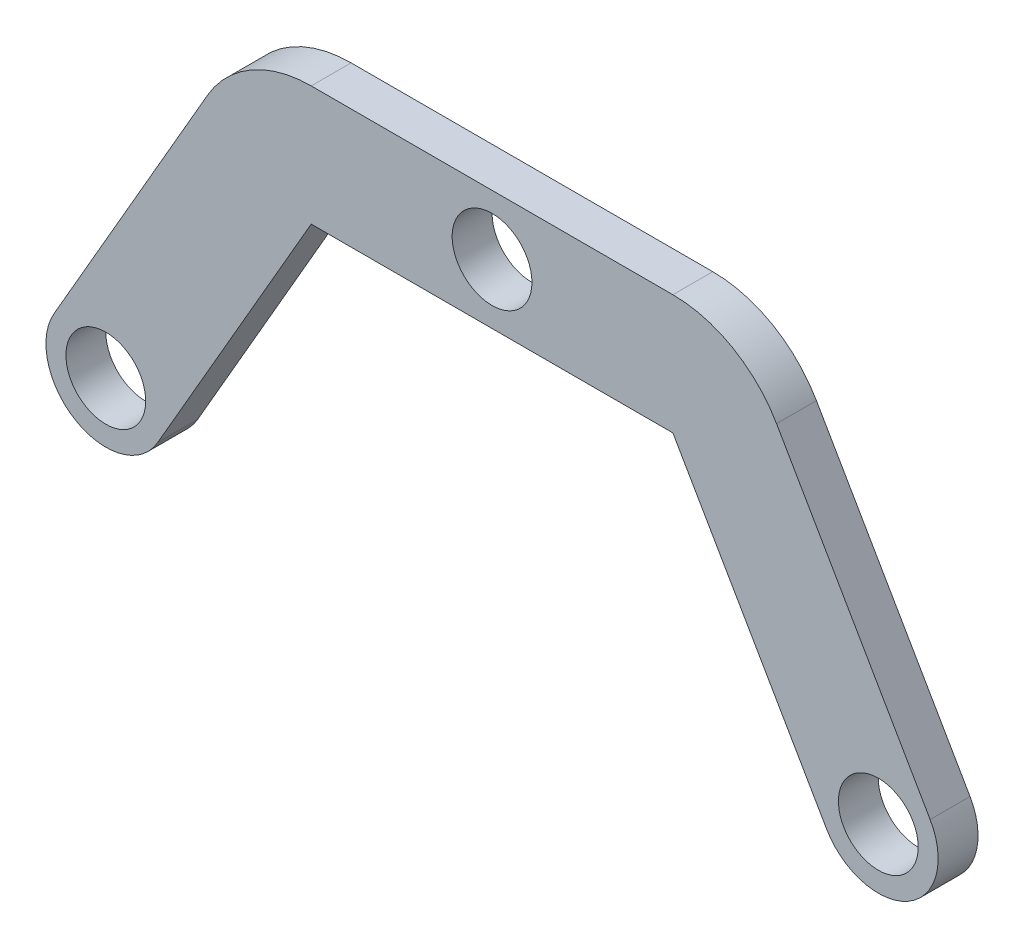
SolidWorks part; units mm, degrees
ref_plane "Front Plane" through (0, 0, 0) normal (0, 0, 1) x (1, 0, 0)
ref_plane "Top Plane" through (0, 0, 0) normal (0, 1, 0) x (1, 0, 0)
ref_plane "Right Plane" through (0, 0, 0) normal (1, 0, 0) x (0, 0, -1)
sketch "Sketch1" plane through (0, 0, 0) normal (0, 0, 1) x (1, 0, 0)
  line L0 (0, -15) -> (0, 15) construction
  line L1 (45.3286, 15) -> (-45.3286, 15)
  line L2 (45.3286, -15) -> (-45.3286, -15)
  line L3 (-45.3286, -15) -> (-83.8292, -81.6849)
  line L5 (-109.81, -66.6849) -> (-71.3094, 0)
  line L6 (109.81, -66.6849) -> (71.3094, 0)
  line L8 (45.3286, -15) -> (83.8292, -81.6849)
  arc A1 (-71.3094, 0) -> (-45.3286, 15) centre (-45.3286, -15) cw
  arc A2 (71.3094, 0) -> (45.3286, 15) centre (45.3286, -15) ccw
  circle A3 centre (-96.8196, -74.1849) radius 15 construction
  arc A5 (-109.81, -66.6849) -> (-83.8292, -81.6849) centre (-96.8196, -74.1849) ccw
  arc A6 (83.8292, -81.6849) -> (109.81, -66.6849) centre (96.8196, -74.1849) ccw
  point P4 (0, 0)
  point P6 (0, 15)
  point P10 (0, -15)
  point P11 (0, 0)
  point P21 (0, 0)
  point P22 (0, 0)
  point P24 (0, 0)
  point P25 (0, 0)
  point P26 (0, 0)
  point P27 (0, 0)
  point P29 (0, 0)
  point P30 (0, 0)
  point P32 (100, -86.6025)
  dimension "D1" = 30
  dimension "D3" = 120
extrude "Boss-Extrude1" add sketch "Sketch1" along normal blind 10
sketch "Sketch2" plane through (0, 0, 10) normal (0, 0, 1) x (1, 0, 0)
  circle A0 centre (0, 0) radius 10
  circle A1 centre (-96.8196, -74.1849) radius 10
  circle A2 centre (96.8196, -74.1849) radius 10
extrude "Cut-Extrude1" cut sketch "Sketch2" against normal up to surface (10 mm away) up to face at (0, -31.5759, 0)
